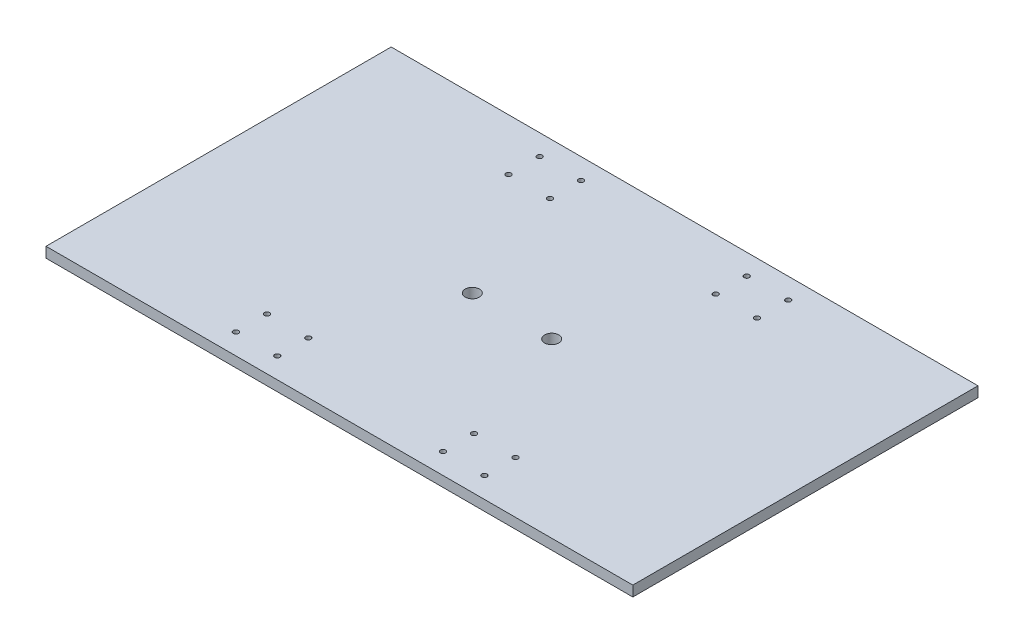
SolidWorks part; units mm, degrees
ref_plane "Front Plane" through (0, 0, 0) normal (0, 0, 1) x (1, 0, 0)
ref_plane "Top Plane" through (0, 0, 0) normal (0, 1, 0) x (1, 0, 0)
ref_plane "Right Plane" through (0, 0, 0) normal (1, 0, 0) x (0, 0, -1)
sketch "Sketch1" plane through (0, 0, 0) normal (0, 1, 0) x (1, 0, 0)
  line L0 (-1000, 0) -> (49000, 0) construction
  line L1 (-170, 100) -> (170, 100)
  line L2 (-170, 100) -> (-170, -100)
  line L3 (-170, -100) -> (170, -100)
  line L4 (170, 100) -> (170, -100)
  line L5 (-170, 100) -> (170, -100) construction
  line L6 (-170, -100) -> (170, 100) construction
  line L7 (0, -1000) -> (0, 49000) construction
  line L8 (60, -1000) -> (60, 49000) construction
  line L9 (-60, -1000) -> (-60, 49000) construction
  line L11 (48, 88) -> (72, 88) construction
  line L12 (48, 88) -> (48, 70) construction
  line L13 (48, 70) -> (72, 70) construction
  line L14 (72, 88) -> (72, 70) construction
  line L15 (48, 88) -> (72, 70) construction
  line L16 (48, 70) -> (72, 88) construction
  circle A0 centre (-23, 0) radius 4.1
  circle A1 centre (23, 0) radius 4.1
  circle A2 centre (72, 88) radius 1.5
  circle A3 centre (48, 88) radius 1.5
  circle A4 centre (72, 70) radius 1.5
  circle A5 centre (48, 70) radius 1.5
  circle A6 centre (-48, 70) radius 1.5
  circle A7 centre (-72, 70) radius 1.5
  circle A8 centre (-48, 88) radius 1.5
  circle A9 centre (-72, 88) radius 1.5
  circle A10 centre (-72, -88) radius 1.5
  circle A11 centre (-48, -88) radius 1.5
  circle A12 centre (-72, -70) radius 1.5
  circle A13 centre (-48, -70) radius 1.5
  circle A14 centre (48, -70) radius 1.5
  circle A15 centre (72, -70) radius 1.5
  circle A16 centre (48, -88) radius 1.5
  circle A17 centre (72, -88) radius 1.5
  point P0 (0, 0)
  point P18 (60, 79)
  dimension "D5" = 8.2
  dimension "D6" = 23
  dimension "D10" = 3
  dimension "D12" = 18
  dimension "D1" = 200
  dimension "D2" = 340
  dimension "D7" = 24
  dimension "D8" = 18
  dimension "D9" = 70
  dimension "D3" = 60
  dimension "D4" = 60
  dimension "D11" = 2
extrude "Boss-Extrude1" add sketch "Sketch1" along normal blind 6
